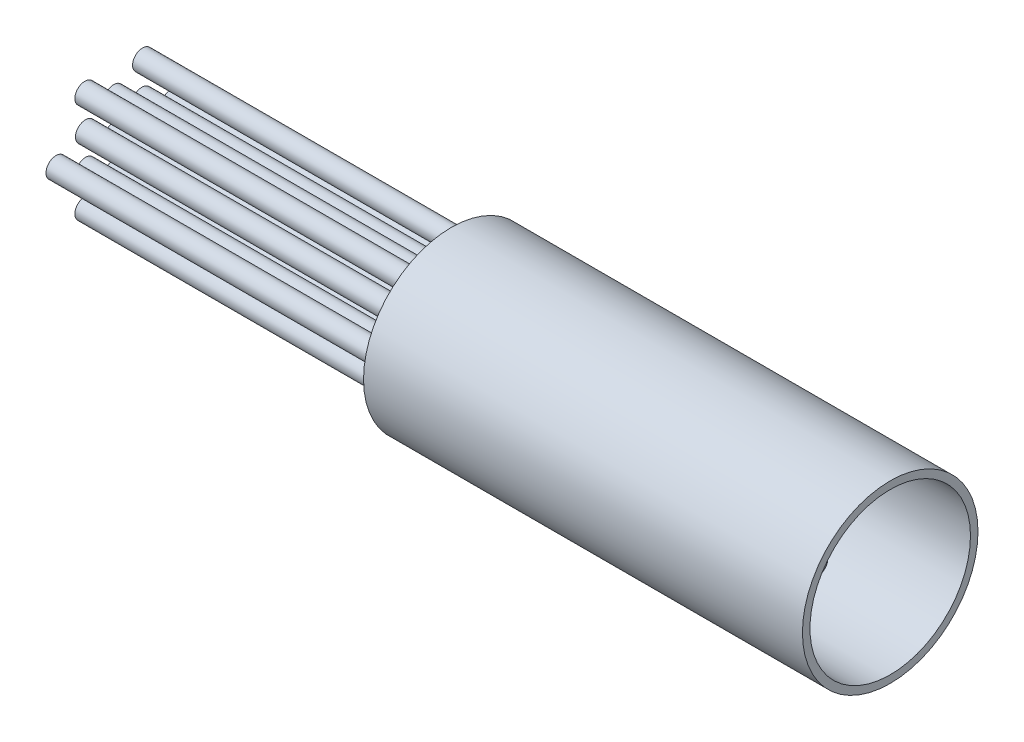
SolidWorks part; units mm, degrees
ref_plane "Front Plane" through (0, 0, 0) normal (0, 0, 1) x (1, 0, 0)
ref_plane "Top Plane" through (0, 0, 0) normal (0, 1, 0) x (1, 0, 0)
ref_plane "Right Plane" through (0, 0, 0) normal (1, 0, 0) x (0, 0, -1)
sketch "Sketch1" plane through (0, 0, 0) normal (1, 0, 0) x (0, 0, -1)
  circle A2 centre (0, 0) radius 35
  circle A3 centre (0, 0) radius 32
  dimension "D1" = 64
  dimension "D3" = 70
extrude "Boss-Extrude2" add sketch "Sketch1" along normal blind 175
sketch "Sketch5" plane through (0, 0, 0) normal (-1, 0, 0) x (0, 0, 1)
  circle A0 centre (0, 0) radius 3
  circle A1 centre (0, 0) radius 4
  dimension "D1" = 6
  dimension "D2" = 8
extrude "Boss-Extrude3" add sketch "Sketch5" against normal blind 134.6 and the other way blind 134.6 separate body
sketch "Sketch7" plane through (0, 0, 0) normal (-1, 0, 0) x (0, 0, 1)
  circle A0 centre (0, 13) radius 3
  circle A1 centre (0, 13) radius 4
  circle A2 centre (11.2583, 6.5) radius 4
  circle A3 centre (11.2583, 6.5) radius 3
  circle A4 centre (11.2583, -6.5) radius 4
  circle A5 centre (11.2583, -6.5) radius 3
  circle A6 centre (0, -13) radius 4
  circle A7 centre (0, -13) radius 3
  circle A8 centre (-11.2583, -6.5) radius 4
  circle A9 centre (-11.2583, -6.5) radius 3
  circle A10 centre (-11.2583, 6.5) radius 4
  circle A11 centre (-11.2583, 6.5) radius 3
  dimension "D1" = 6
  dimension "D2" = 8
  dimension "D3" = 13
  dimension "D5" = 13
  dimension "D4" = 6
extrude "Boss-Extrude4" add sketch "Sketch7" against normal blind 134.6 and the other way blind 134.6 separate body
sketch "Sketch9" plane through (0, 0, 0) normal (-1, 0, 0) x (0, 0, 1)
  line L0 (11.2583, 6.5) -> (0, 0) construction
  line L1 (0, 0) -> (11.5, 19.9186) construction
  circle A0 centre (11.5, 19.9186) radius 4
  circle A1 centre (11.5, 19.9186) radius 3
  circle A2 centre (23, 0) radius 4
  circle A3 centre (23, 0) radius 3
  circle A4 centre (11.5, -19.9186) radius 4
  circle A5 centre (11.5, -19.9186) radius 3
  circle A6 centre (-11.5, -19.9186) radius 4
  circle A7 centre (-11.5, -19.9186) radius 3
  circle A8 centre (-23, 0) radius 4
  circle A9 centre (-23, 0) radius 3
  circle A10 centre (-11.5, 19.9186) radius 4
  circle A11 centre (-11.5, 19.9186) radius 3
  dimension "D2" = 6
  dimension "D3" = 8
  dimension "D1" = 23
  dimension "D4" = 30
  dimension "D6" = 23
  dimension "D7" = 23
  dimension "D5" = 6
extrude "Boss-Extrude5" add sketch "Sketch9" against normal blind 134.6 and the other way blind 134.6 separate body
